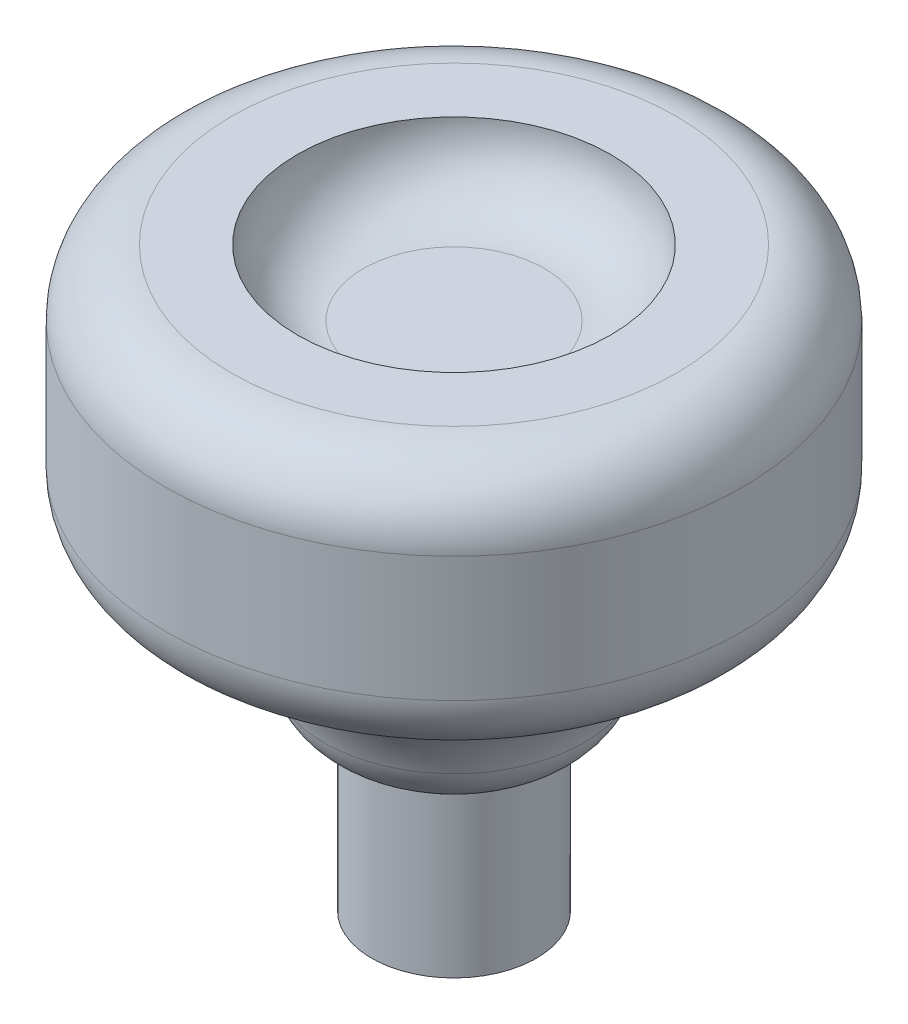
SolidWorks part; units mm, degrees
ref_plane "Front" through (0, 0, 0) normal (0, 0, 1) x (1, 0, 0)
ref_plane "Top" through (0, 0, 0) normal (0, 1, 0) x (-1, 0, 0)
ref_plane "Right" through (0, 0, 0) normal (1, 0, 0) x (0, 0, -1)
sketch "Sketch1" plane through (0, 0, 0) normal (0, 0, 1) x (1, 0, 0)
  line L0 (0, 0) -> (0, 36.2882) construction
  line L1 (0, 0) -> (0, 22.225)
  line L2 (0, 22.225) -> (11.1125, 22.225)
  line L3 (11.1125, 12.7) -> (11.1125, 22.225)
  line L4 (4.7625, 6.35) -> (3.175, 6.35)
  line L5 (3.175, 6.35) -> (3.175, 0)
  line L6 (3.175, 0) -> (0, 0)
  arc A0 (11.1125, 22.225) -> (11.1125, 12.7) centre (11.1125, 17.4625) cw
  arc A1 (11.1125, 12.7) -> (4.7625, 6.35) centre (11.1125, 6.35) ccw
  dimension "D5" = 6.35
  dimension "D6" = 4.7625
  dimension "D1" = 6.35
  dimension "D2" = 4.7625
  dimension "D3" = 6.35
  dimension "D4" = 15.875
revolve "Base-Revolve" add sketch "Sketch1" angle 360 about L0 region at (4.5215, 13.9357, 0)
fillet "Fillet1" radius 2.54 3 edges at (0, 12.7, -11.1125) (0, 6.35, -4.7625) (0, 22.225, -11.1125)
sketch "Sketch2" plane through (0, 22.225, 0) normal (0, 1, 0) x (1, 0, 0)
  circle A0 centre (0, 0) radius 6.0325
  circle A1 centre (0, 0) radius 8.5725 construction
  dimension "D1" = 2.54
extrude "Cut-Extrude1" cut sketch "Sketch2" against normal blind 2.54
fillet "Fillet2" radius 2.54 1 edges at (0, 19.685, 6.0325)
